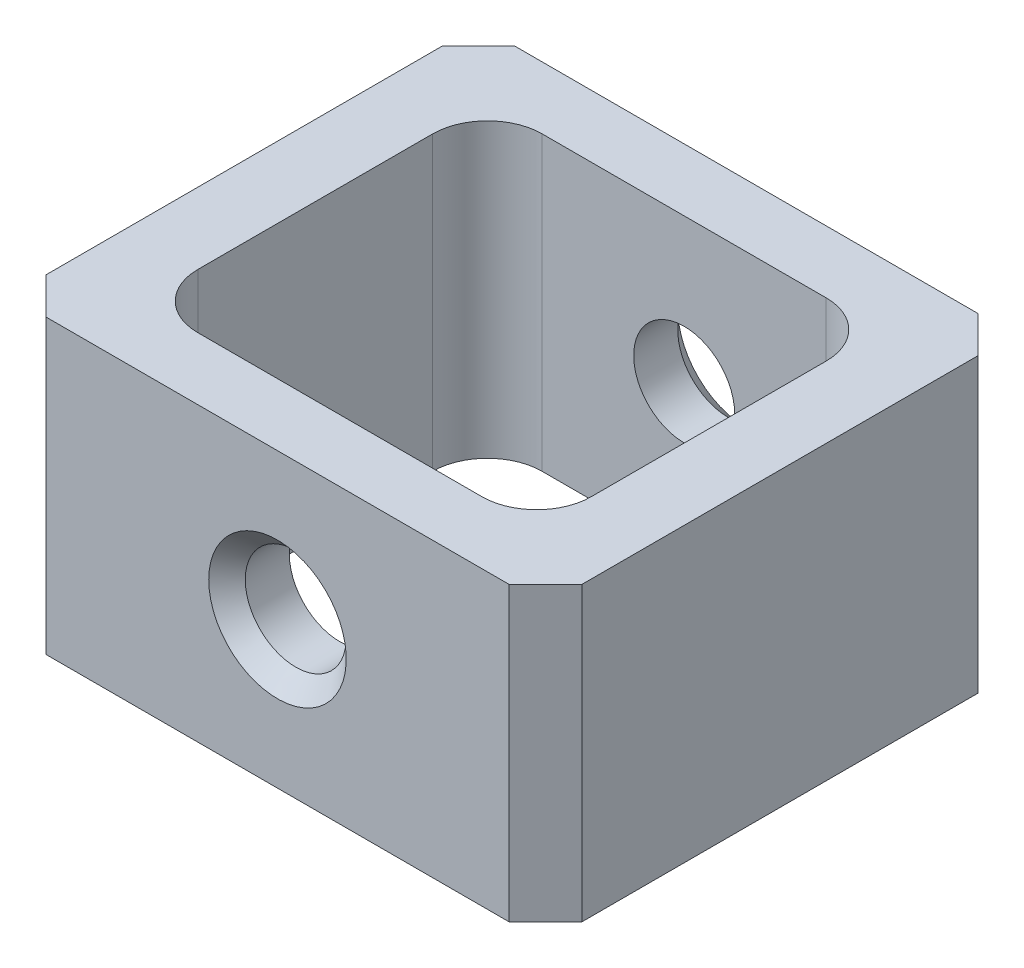
SolidWorks part; units mm, degrees
ref_plane "Front Plane" through (0, 0, 0) normal (0, 0, 1) x (1, 0, 0)
ref_plane "Top Plane" through (0, 0, 0) normal (0, 1, 0) x (1, 0, 0)
ref_plane "Right Plane" through (0, 0, 0) normal (1, 0, 0) x (0, 0, -1)
sketch "Sketch1" plane through (0, 0, 0) normal (0, 1, 0) x (1, 0, 0)
  line L0 (73.3623, 54.192) -> (63.3623, 64.192)
  line L1 (63.3623, -64.192) -> (-63.3623, -64.192)
  line L2 (73.3623, -54.192) -> (73.3623, 54.192)
  line L3 (63.3623, 64.192) -> (-63.3623, 64.192)
  line L4 (-73.3623, -54.192) -> (-73.3623, 54.192)
  line L5 (73.3623, -64.192) -> (-73.3623, 64.192) construction
  line L6 (73.3623, 64.192) -> (-73.3623, -64.192) construction
  line L7 (38.8585, -47.1262) -> (-38.8585, -47.1262)
  line L8 (53.8585, -32.1262) -> (53.8585, 32.1262)
  line L9 (38.8585, 47.1262) -> (-38.8585, 47.1262)
  line L10 (-53.8585, -32.1262) -> (-53.8585, 32.1262)
  line L11 (53.8585, -47.1262) -> (-53.8585, 47.1262) construction
  line L12 (53.8585, 47.1262) -> (-53.8585, -47.1262) construction
  line L13 (-63.3623, 64.192) -> (-73.3623, 54.192)
  line L14 (-63.3623, -64.192) -> (-73.3623, -54.192)
  line L15 (73.3623, -54.192) -> (63.3623, -64.192)
  arc A0 (-38.8585, -47.1262) -> (-53.8585, -32.1262) centre (-38.8585, -32.1262) cw
  arc A1 (53.8585, 32.1262) -> (38.8585, 47.1262) centre (38.8585, 32.1262) ccw
  arc A2 (38.8585, -47.1262) -> (53.8585, -32.1262) centre (38.8585, -32.1262) ccw
  arc A3 (-38.8585, 47.1262) -> (-53.8585, 32.1262) centre (-38.8585, 32.1262) ccw
  point P0 (0, 0)
  point P5 (0, 0)
  dimension "D1" = 15
extrude "Boss-Extrude1" add sketch "Sketch1" along normal blind 80
sketch "Sketch2" plane through (0, 0, -64.192) normal (0, 0, -1) x (1, 0, 0)
  line L0 (-73.3623, -80) -> (-73.3623, 0) construction
  circle A0 centre (0, -40) radius 13.8192
  point P5 (-73.3623, -40)
extrude "Cut-Extrude1" cut sketch "Sketch2" against normal through all
chamfer "Chamfer1" distance 5 angle 45 2 edges at (0, 53.8192, 64.192) (0, 53.8192, -64.192)
ref_plane "Plane1" through (0, 0, -74.192) normal (0, 0, -1) x (1, 0, 0)
sketch "Sketch4" plane through (0, 0, -74.192) normal (0, 0, -1) x (1, 0, 0)
  text T0 "<b>KIMODA DESIGNS</b>" font "Century Gothic" height 8
  point P1 (0, 0)
wrap "Wrap1" sketch "Sketch4" wrap type scribe source sketch "Sketch4" face at (18.8192, 40, -64.192)
